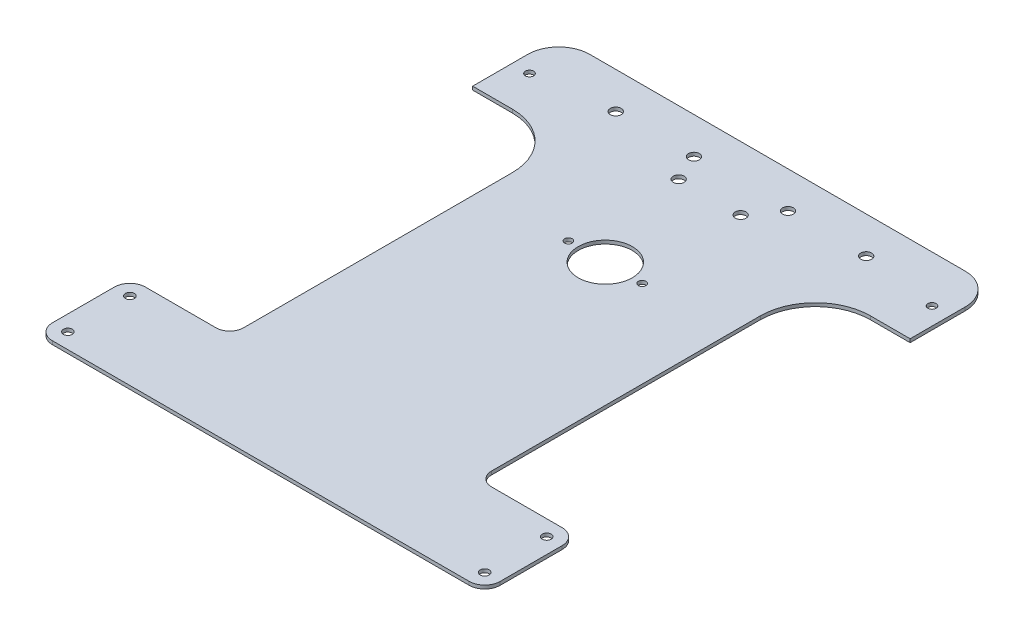
SolidWorks part; units mm, degrees
material "Thornel VCB-20 Carbon Cloth"
ref_plane "Front" through (0, 0, 0) normal (0, 0, 1) x (1, 0, 0)
ref_plane "Top" through (0, 0, 0) normal (0, 1, 0) x (1, 0, 0)
ref_plane "Right" through (0, 0, 0) normal (1, 0, 0) x (0, 0, -1)
ref_axis "X" through (-80.9, 0, 0) along (1, 0, 0)
ref_axis "Y" through (0, -50, 0) along (0, 1, 0)
ref_axis "Z" through (0, 0, -80.9) along (0, 0, 1)
sketch "Sketch1" plane through (0, 0, 0) normal (0, 1, 0) x (1, 0, 0)
  line L0 (-65, -150) -> (65, -150)
  line L1 (-65, -150) -> (-65, -123)
  line L2 (-65, -123) -> (-36, -123)
  line L3 (-36, -123) -> (-36, -25)
  line L4 (-36, -25) -> (-63.5, -25)
  line L5 (-63.5, -25) -> (-63.5, 0)
  line L6 (-63.5, 0) -> (63.5, 0)
  line L7 (63.5, 0) -> (63.5, -25)
  line L8 (63.5, -25) -> (36, -25)
  line L9 (36, -25) -> (36, -123)
  line L10 (36, -123) -> (65, -123)
  line L11 (65, -123) -> (65, -150)
  line L12 (0, -150) -> (0, 0) construction
  dimension "D1" = 130
  dimension "D2" = 72
  dimension "D5" = 25
  dimension "D6" = 127
  dimension "D7" = 150
  dimension "D3" = 27
  dimension "D4" = 90
extrude "Boss-Extrude1" add sketch "Sketch1" along normal mid plane 1
hole_wizard "M2 Clearance Hole1" positions "Sketch2" profile "Sketch3" hole size "M2" standard "ANSI Metric" end condition up to next
sketch "Sketch2" plane through (0, 0.5, 0) normal (0, 1, 0) x (1, 0, 0)
  line L0 (-60.5, -145.5) -> (60.5, -145.5) construction
  line L2 (-65, -150) -> (65, -150) construction
  line L3 (-65, -123) -> (-65, -150) construction
  line L4 (65, -150) -> (65, -123) construction
  line L5 (-60.5, -127.5) -> (-60.5, -145.5) construction
  line L8 (60.5, -127.5) -> (60.5, -145.5) construction
  point P0 (-60.5, -145.5)
  point P2 (60.5, -145.5)
  point P15 (-60.5, -127.5)
  point P17 (60.5, -127.5)
  dimension "D1" = 4.5
  dimension "D2" = 4.5
  dimension "D3" = 4.5
  dimension "D4" = 18
sketch "Sketch3" plane through (-60.5, 0.5, 145.5) normal (1, 0, 0) x (0, 0, 1)
  line L0 (0, 0) -> (0, 1)
  line L1 (0, 1) -> (1.3, 1)
  line L2 (1.3, 1) -> (1.3, 0)
  line L5 (1.3, 0) -> (0, 0)
  line L11 (0, -6.35) -> (0, 107.95) construction
  dimension "Thru Hole Dia." = 2.6
  dimension "Thru Hole Depth" = 1
fillet "Fillet1" radius 4.5 4 edges at (65, 0, 150) (-65, 0, 150) (65, 0, 123) (-65, 0, 123)
fillet "Fillet2" radius 9 2 edges at (63.5, 0, 0) (-63.5, 0, 0)
hole_wizard "M2 Clearance Hole2" positions "Sketch7" profile "Sketch8" hole size "M2" standard "ANSI Metric" end condition up to next
sketch "Sketch7" plane through (0, 0.5, 0) normal (0, 1, 0) x (1, 0, 0)
  line L0 (-58.42, -13.57) -> (58.42, -13.57) construction
  line L2 (0, 0) -> (0, -13.57) construction
  line L3 (54.5, 0) -> (-54.5, 0) construction
  line L5 (-63.5, -25) -> (-36, -25) construction
  point P0 (-58.42, -13.57)
  point P2 (58.42, -13.57)
  dimension "D1" = 116.84
  dimension "D2" = 11.43
sketch "Sketch8" plane through (-58.42, 0.5, 13.57) normal (1, 0, 0) x (0, 0, 1)
  line L0 (0, 0) -> (0, 1)
  line L1 (0, 1) -> (1.2, 1)
  line L2 (1.2, 1) -> (1.2, 0)
  line L5 (1.2, 0) -> (0, 0)
  line L11 (0, -6.35) -> (0, 107.95) construction
  dimension "Thru Hole Dia." = 2.4
  dimension "Thru Hole Depth" = 1
fillet "Fillet4" radius 4 2 edges at (36, 0, 123) (-36, 0, 123)
fillet "Fillet5" radius 16 2 edges at (36, 0, 25) (-36, 0, 25)
sketch "Sketch13" plane through (0, 0.5, 0) normal (0, 1, 0) x (1, 0, 0)
  line L0 (-38, -131) -> (-38, -142) construction
  line L1 (-35, -131) -> (-35, -142)
  line L3 (38, -131) -> (38, -142) construction
  line L5 (35, -131) -> (35, -142)
  line L6 (-38, -136.5) -> (38, -136.5) construction
  line L7 (0, -136.5) -> (0, 0) construction
  line L8 (54.5, 0) -> (-54.5, 0) construction
  line L11 (-60.5, -127.5) -> (-60.5, -145.5) construction
  line L12 (-60.5, -136.5) -> (-38, -136.5) construction
  line L13 (-38, -128) -> (-45.5, -128)
  line L14 (-38, -145) -> (-45.5, -145)
  line L15 (38, -128) -> (45.5, -128)
  line L16 (38, -145) -> (45.5, -145)
  line L17 (48.5, -131) -> (48.5, -142)
  line L18 (-48.5, -131) -> (-48.5, -142)
  line L19 (-35, -136.5) -> (-48.5, -136.5) construction
  line L20 (35, -136.5) -> (48.5, -136.5) construction
  arc A0 (-35, -131) -> (-38, -128) centre (-38, -131) ccw
  arc A1 (-38, -145) -> (-35, -142) centre (-38, -142) ccw
  arc A2 (38, -128) -> (35, -131) centre (38, -131) ccw
  arc A3 (35, -142) -> (38, -145) centre (38, -142) ccw
  circle A4 centre (-60.5, -127.5) radius 1.3 construction
  arc A5 (45.5, -128) -> (48.5, -131) centre (45.5, -131) cw
  arc A6 (48.5, -142) -> (45.5, -145) centre (45.5, -142) cw
  arc A7 (-45.5, -128) -> (-48.5, -131) centre (-45.5, -131) ccw
  arc A8 (-48.5, -142) -> (-45.5, -145) centre (-45.5, -142) ccw
  point P2 (-38, -136.5)
  point P8 (38, -136.5)
  dimension "D5" = 3.5
  dimension "D1" = 17
  dimension "D2" = 13.5
  dimension "D3" = 70
extrude "Cut-Extrude4" [suppressed] cut sketch "Sketch13" against normal through all
hole_wizard "M2 Clearance Hole3" positions "Sketch14" profile "Sketch15" hole size "M2" standard "ANSI Metric" end condition up to next
sketch "Sketch14" plane through (0, 0.5, 0) normal (0, 1, 0) x (1, 0, 0)
  line L2 (-10.7, -50) -> (10.7, -50) construction
  line L3 (0, 0) -> (0, -50) construction
  line L4 (54.5, 0) -> (-54.5, 0) construction
  point P0 (-10.7, -50)
  point P2 (10.7, -50)
  dimension "D1" = 21.4
  dimension "D2" = 50
sketch "Sketch15" plane through (-10.7, 0.5, 50) normal (1, 0, 0) x (0, 0, 1)
  line L0 (0, 0) -> (0, 1)
  line L1 (0, 1) -> (1.1, 1)
  line L2 (1.1, 1) -> (1.1, 0)
  line L5 (1.1, 0) -> (0, 0)
  line L11 (0, -6.35) -> (0, 107.95) construction
  dimension "Thru Hole Dia." = 2.2
  dimension "Thru Hole Depth" = 1
sketch "Sketch17" plane through (0, 0.5, 0) normal (0, 1, 0) x (1, 0, 0)
  line L0 (-36.35, -10.6) -> (-13.65, -10.6) construction
  line L1 (-13.65, -10.6) -> (13.65, -10.6) construction
  line L2 (13.65, -10.6) -> (36.35, -10.6) construction
  line L3 (7.8, -18.5) -> (-10.2, -18.5) construction
  line L4 (0, -10.6) -> (0, 0) construction
  line L5 (-25, -10.6) -> (-25, -15.252) construction
  line L6 (0, -10.6) -> (0, -18.5) construction
  line L7 (54.5, 0) -> (-54.5, 0) construction
  line L8 (25, -10.6) -> (25, -14.0507) construction
  circle A2 centre (7.8, -18.5) radius 1.575
  circle A3 centre (-10.2, -18.5) radius 1.575
  circle A8 centre (36.35, -10.6) radius 1.575
  circle A9 centre (13.65, -10.6) radius 1.575
  circle A10 centre (-13.65, -10.6) radius 1.575
  circle A11 centre (-36.35, -10.6) radius 1.575
  point P22 (-1.2, -18.5)
  dimension "D7" = 3.15
  dimension "D1" = 22.7
  dimension "D2" = 50
  dimension "D4" = 10.6
  dimension "D5" = 18.5
  dimension "D6" = 1.2
  dimension "D8" = 18
extrude "Cut-Extrude6" cut sketch "Sketch17" against normal through all
sketch "Sketch18" plane through (0, 0.5, 0) normal (0, 1, 0) x (1, 0, 0)
  line L0 (-10.7, -50) -> (10.7, -50) construction
  circle A0 centre (0, -50) radius 7.85
  circle A6 centre (-10.7, -50) radius 1.1 construction
  circle A8 centre (10.7, -50) radius 1.1 construction
  point P1 (8.3, -40.0527)
  dimension "D3" = 15.7
extrude "Cut-Extrude7" cut sketch "Sketch18" against normal up to next
equation "\"D1@Sketch1\"=92+38"
